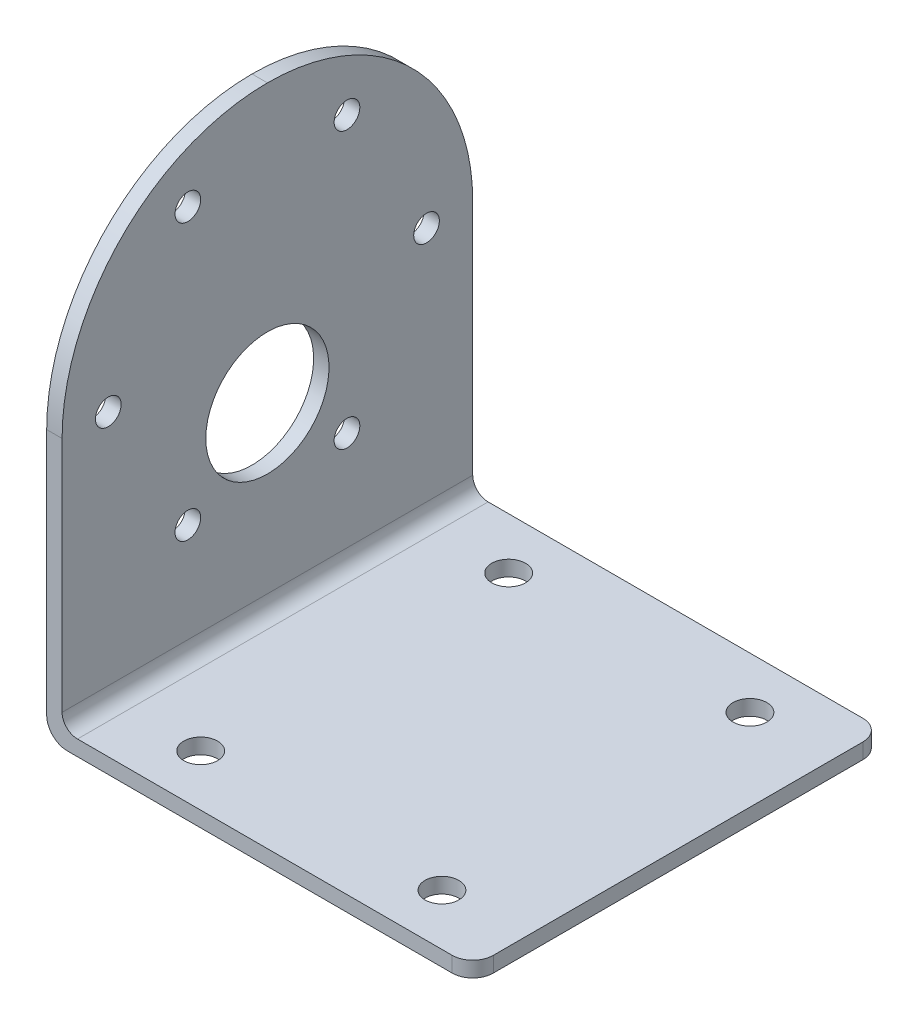
SolidWorks part; units mm, degrees
ref_plane "Спереди" through (0, 0, 0) normal (0, 0, 1) x (1, 0, 0)
ref_plane "Сверху" through (0, 0, 0) normal (0, 1, 0) x (1, 0, 0)
ref_plane "Справа" through (0, 0, 0) normal (1, 0, 0) x (0, 0, -1)
sketch "Эскиз1" plane through (0, 0, 0) normal (0, 1, 0) x (1, 0, 0)
  line L1 (20.75, -20) -> (-20.75, -20)
  line L2 (20.75, -20) -> (20.75, 20)
  line L3 (20.75, 20) -> (-20.75, 20)
  line L4 (-20.75, -20) -> (-20.75, 20)
  line L5 (20.75, -20) -> (-20.75, 20) construction
  line L6 (20.75, 20) -> (-20.75, -20) construction
  point P0 (0, 0)
extrude "Бобышка-Вытянуть1" add sketch "Эскиз1" along normal blind 1.5
sketch "Эскиз2" plane through (0, 1.5, 0) normal (0, 1, 0) x (1, 0, 0)
  line L0 (-20.75, -20) -> (20.75, -20) construction
  line L1 (-20.75, 20) -> (-19.25, 20)
  line L2 (-20.75, 20) -> (-20.75, -20)
  line L3 (-20.75, -20) -> (-19.25, -20)
  line L4 (-19.25, 20) -> (-19.25, -20)
extrude "Бобышка-Вытянуть2" add sketch "Эскиз2" along normal blind 44.6
fillet "Скругление2" radius 20 1 edges at (-20, 46.1, 20)
fillet "Скругление3" radius 20 1 edges at (-20, 46.1, -20)
sketch "Эскиз3" plane through (-20.75, 0, 0) normal (-1, 0, 0) x (0, 0, 1)
  line L0 (20, 26.1) -> (-20, 26.1) construction
  line L1 (0, 46.1) -> (0, 26.1) construction
  arc A0 (0, 46.1) -> (-20, 26.1) centre (0, 26.1) ccw construction
  circle A2 centre (-15.5, 26.1) radius 1.25
  circle A3 centre (-7.75, 39.5234) radius 1.25
  circle A4 centre (7.75, 39.5234) radius 1.25
  circle A5 centre (15.5, 26.1) radius 1.25
  circle A6 centre (7.75, 12.6766) radius 1.25
  circle A7 centre (-7.75, 12.6766) radius 1.25
  circle A8 centre (0, 19.1) radius 6
  point P25 (0, 26.1)
  dimension "D1" = 6
extrude "Вырез-Вытянуть1" cut sketch "Эскиз3" against normal blind 44.6
sketch "Эскиз4" plane through (0, 0, 0) normal (0, -1, 0) x (1, 0, 0)
  line L1 (20.75, 20) -> (20.75, -20) construction
  line L3 (-20.75, 20) -> (20.75, 20) construction
  line L4 (12.75, 20) -> (12.75, -19.3855) construction
  line L5 (-20.75, -20) -> (-20.75, 20) construction
  line L6 (-20.75, 15) -> (20.75, 15) construction
  circle A0 centre (12.75, 15) radius 1.65
  circle A1 centre (-10.75, 15) radius 1.65
  circle A2 centre (-10.75, -15) radius 1.65
  circle A3 centre (12.75, -15) radius 1.65
  dimension "D1" = 2
  dimension "D2" = 2
extrude "Вырез-Вытянуть2" cut sketch "Эскиз4" against normal blind 44.6
fillet "Скругление5" radius 2 2 edges at (20.75, 0.75, -20) (20.75, 0.75, 20)
fillet "Скругление6" radius 2 1 edges at (-20.75, 0, 0)
fillet "Скругление7" radius 1.5 1 edges at (-19.25, 1.5, 0)
